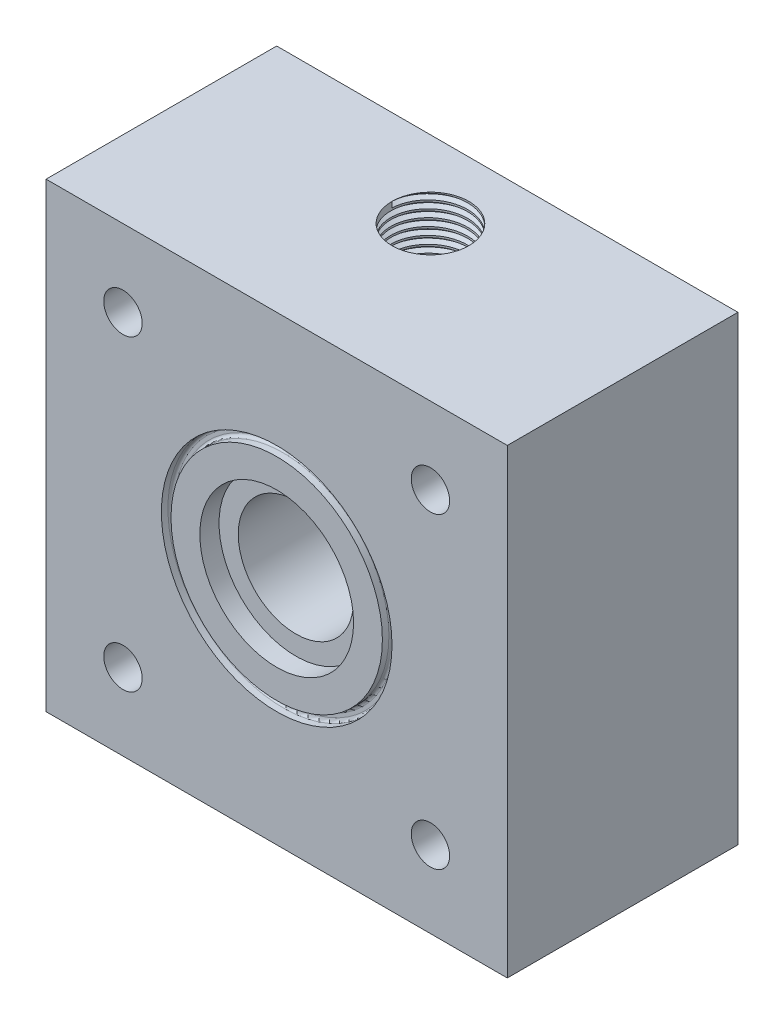
SolidWorks part; units mm, degrees
ref_plane "Front Plane" through (0, 0, 0) normal (0, 0, 1) x (1, 0, 0)
ref_plane "Top Plane" through (0, 0, 0) normal (0, 1, 0) x (1, 0, 0)
ref_plane "Right Plane" through (0, 0, 0) normal (1, 0, 0) x (0, 0, -1)
sketch "Sketch2" plane through (0, 0, 0) normal (0, 0, 1) x (1, 0, 0)
  line L1 (-38.1, -38.1) -> (38.1, -38.1)
  line L2 (-38.1, -38.1) -> (-38.1, 38.1)
  line L3 (-38.1, 38.1) -> (38.1, 38.1)
  line L4 (38.1, -38.1) -> (38.1, 38.1)
  line L5 (-38.1, -38.1) -> (38.1, 38.1) construction
  line L6 (-38.1, 38.1) -> (38.1, -38.1) construction
  point P0 (0, 0)
  dimension "D1" = 76.2
  dimension "D2" = 76.2
extrude "Boss-Extrude1" add sketch "Sketch2" along normal blind 38.1
sketch "Sketch3" plane through (0, 0, 0) normal (0, 0, -1) x (-1, 0, 0)
  circle A0 centre (0, 0) radius 25.4
  circle A1 centre (0, 0) radius 17.4625
  dimension "D1" = 50.8
  dimension "D2" = 34.925
extrude "Cut-Extrude1" cut sketch "Sketch3" against normal blind 3.81
sketch "Sketch5" plane through (0, 38.1, 0) normal (0, 1, 0) x (1, 0, 0)
  line L0 (38.1, 0) -> (-38.1, 0) construction
  circle A0 centre (0, -12.7) radius 6.35
  point P4 (0, 0)
  dimension "D1" = 12.7
  dimension "D2" = 12.7
extrude "Cut-Extrude3" cut sketch "Sketch5" against normal blind 38.1
thread "Thread1" pitch 1.27 method cut profile "Thread Profile2" start angle 0, offset 0, length 12.7, pitch 1.27, diameter 12.7
ref_plane "Plane2" through (-6.35, 38.1, 12.7) normal (0, 0, 1) x (-1, 0, 0)
sketch "Thread Profile2" plane through (-6.35, 38.1, 12.7) normal (0, 0, 1) x (-1, 0, 0)
  line L0 (0, 0) -> (0, 1.27) construction
  line L1 (0, 0) -> (0.6874, 0.3969)
  line L2 (0.6874, 0.3969) -> (0.6874, 0.5556)
  line L3 (0.6874, 0.5556) -> (0, 0.9525)
  line L4 (0.6874, 0.4762) -> (0, 0.4762) construction
  line L11 (0, 0) -> (0, 0.9525)
  point P2 (0, 0)
  dimension "Pitch" = 1.27
  dimension "Profile_Angle" = 60
  dimension "Profile_Land" = 0.1588
  dimension "Profile_Height" = 0.6874
sketch "Sketch17" plane through (0, 0, 38.1) normal (0, 0, 1) x (1, 0, 0)
  line L0 (-38.1, 38.1) -> (-38.1, -38.1) construction
  line L1 (38.1, 38.1) -> (-38.1, 38.1) construction
  circle A0 centre (-25.4, 25.4) radius 3.175
  circle A1 centre (25.4, 25.4) radius 3.175
  circle A2 centre (25.4, -25.4) radius 3.175
  circle A3 centre (-25.4, -25.4) radius 3.175
  point P15 (0, 0)
  dimension "D1" = 6.35
  dimension "D2" = 12.7
  dimension "D3" = 12.7
  dimension "D4" = 4
extrude "Cut-Extrude5" cut sketch "Sketch17" against normal through all
sketch "Sketch18" plane through (0, 0, 38.1) normal (0, 0, 1) x (1, 0, 0)
  circle A0 centre (0, 0) radius 12.7
  dimension "D1" = 25.4
extrude "Cut-Extrude6" cut sketch "Sketch18" against normal blind 3.175
sketch "Sketch21" plane through (0, 0, 0) normal (0, 0, -1) x (-1, 0, 0)
  circle A0 centre (0, 0) radius 9.525
  dimension "D1" = 19.05
extrude "Cut-Extrude9" cut sketch "Sketch21" against normal through all
chamfer "Chamfer1" distance 2.54 angle 45 1 edges at (-9.525, 0, 0)
chamfer "Chamfer2" distance 1.27 angle 45 1 edges at (-25.4, 0, 0)
fillet "Fillet1" radius 1.27 1 edges at (-17.4625, 0, 3.81)
sketch "Sketch22" plane through (0, 0, 38.1) normal (0, 0, 1) x (1, 0, 0)
  circle A0 centre (0, 0) radius 17.4625
  circle A1 centre (0, 0) radius 19.05
  dimension "D1" = 34.925
  dimension "D2" = 38.1
extrude "Cut-Extrude11" cut sketch "Sketch22" against normal blind 1.5875
fillet "Fillet2" radius 0.508 2 edges at (19.05, 0, 36.5125) (17.4625, 0, 36.5125)
equation "\"D2@Sketch3\"=1+3/8"
equation "\"D1@Cut-Extrude6\"= 1 / 8"
equation "\"D1@Sketch22\"=1+3/8"
equation "\"D1@Cut-Extrude11\"=1/16"
